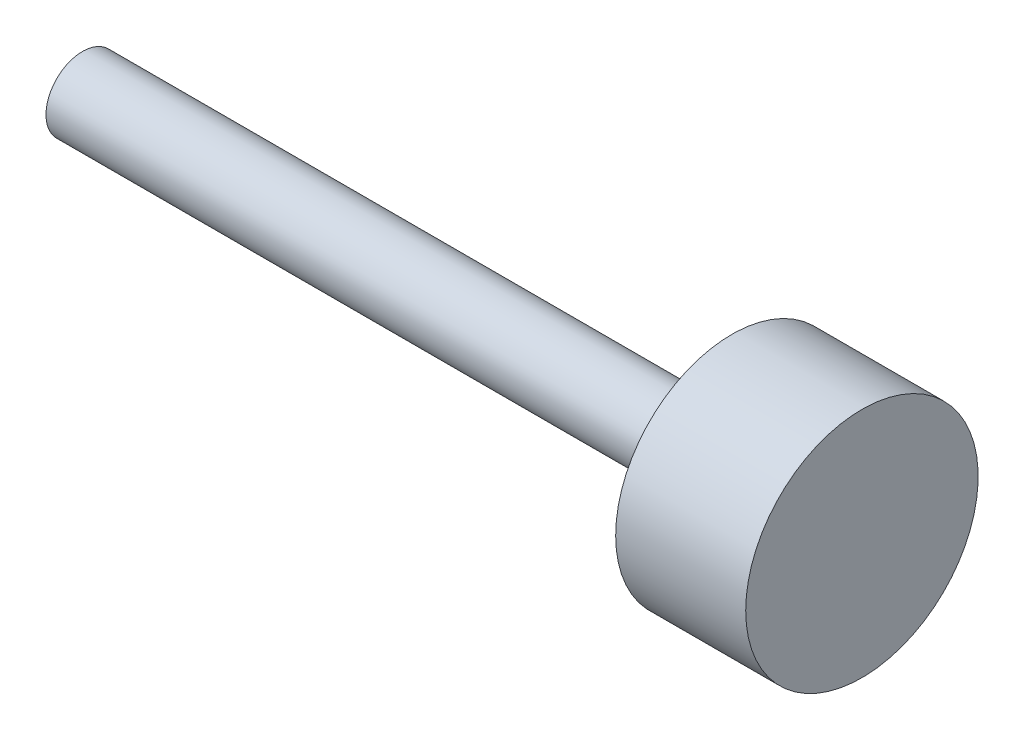
SolidWorks part; units mm, degrees
ref_plane "Front Plane" through (0, 0, 0) normal (0, 0, 1) x (1, 0, 0)
ref_plane "Top Plane" through (0, 0, 0) normal (0, 1, 0) x (1, 0, 0)
ref_plane "Right Plane" through (0, 0, 0) normal (1, 0, 0) x (0, 0, -1)
ref_plane "Plane1" through (-20.5232, 0, 0) normal (1, 0, 0) x (0, 0, -1)
ref_plane "Plane2" through (-20.5232, 0, 0) normal (1, 0, 0) x (0, 0, -1)
sketch "Sketch1" plane through (0, 0, 0) normal (0, 0, 1) x (1, 0, 0)
  line L0 (-22.225, 0) -> (-22.225, 8.001)
  line L1 (-22.225, 8.001) -> (119.9642, 8.001)
  line L2 (119.9642, 8.001) -> (119.9642, 25.4508)
  line L3 (119.9642, 25.4508) -> (148.4376, 25.4508)
  line L4 (148.4376, 25.4508) -> (148.4376, 0)
  line L5 (148.4376, 0) -> (-22.225, 0)
  line L6 (148.4376, 0) -> (-22.225, 0) construction
revolve "Revolve1" add sketch "Sketch1" angle 360 about L6 reverse direction yes
hole_wizard "Hole1" positions "Sketch3" profile "Sketch2" legacy
sketch "Sketch3" plane through (-22.225, 0, 0) normal (-1, 0, 0) x (0, 0, 1)
  point P0 (0, 0)
sketch "Sketch2" plane through (-22.225, 0, 0) normal (0, 1, 0) x (0, 0, 1)
  line L0 (0, 0) -> (0, 30.8737)
  line L1 (0, 30.8737) -> (4.8692, 28.0625)
  line L2 (4.8692, 28.0625) -> (4.8692, 0.6871)
  line L3 (4.8692, 0.6871) -> (5.5562, 0)
  line L4 (5.5562, 0) -> (0, 0)
  line L5 (0, -14.3089) -> (0, 102.4216) construction
  line L6 (0, 30.8737) -> (-4.8692, 28.0625) construction
  line L7 (-4.8692, 0.6871) -> (-5.5562, 0) construction
  dimension "Diameter" = 9.7384
  dimension "Depth" = 28.0625
  dimension "C-Sink Diameter" = 11.1125
  dimension "C-Sink Angle" = 90
  dimension "Drill Angle" = 120
cosmetic thread "Cosmetic Thread1"
ref_plane "Plane3" through (-20.5232, 0, 0) normal (1, 0, 0) x (0, 0, -1)
ref_plane "i1 XY" through (0, 0, 0) normal (0, 0, 1) x (1, 0, 0)
ref_plane "i1 XZ" through (0, 8.001, 0) normal (0, -1, 0) x (-1, 0, 0)
ref_plane "i1 YZ" through (119.9642, 0, 0) normal (1, 0, 0) x (0, 0, -1)
ref_axis "i1 X" through (-80.9, 8.001, 0) along (1, 0, 0)
ref_axis "i1 Y" through (119.9642, -50, 0) along (0, 1, 0)
ref_axis "i1 Z" through (119.9642, 8.001, 80.9) along (0, 0, -1)
sketch3d "i1"
  point P0 (119.9642, 8.001, 0)
ref_plane "i2 XY" through (0, 0, 0) normal (0, 0, 1) x (1, 0, 0)
ref_plane "i2 XZ" through (0, -8.001, 0) normal (0, -1, 0) x (-1, 0, 0)
ref_plane "i2 YZ" through (119.9642, 0, 0) normal (1, 0, 0) x (0, 0, -1)
ref_axis "i2 X" through (-80.9, -8.001, 0) along (1, 0, 0)
ref_axis "i2 Y" through (119.9642, -50, 0) along (0, 1, 0)
ref_axis "i2 Z" through (119.9642, -8.001, 80.9) along (0, 0, -1)
sketch3d "i2"
  point P0 (119.9642, -8.001, 0)
ref_plane "to_rod_guide XY" through (-20.5232, 0, 0) normal (-1, 0, 0) x (0, 0, 1)
ref_plane "to_rod_guide XZ" through (0, 0, 0) normal (0, 1, 0) x (1, 0, 0)
ref_plane "to_rod_guide YZ" through (0, 0, 0) normal (0, 0, -1) x (-1, 0, 0)
ref_axis "to_rod_guide X" through (-20.5232, 0, 80.9) along (0, 0, -1)
ref_axis "to_rod_guide Y" through (-20.5232, 50, 0) along (0, -1, 0)
ref_axis "to_rod_guide Z" through (-80.9, 0, 0) along (1, 0, 0)
sketch3d "to_rod_guide"
  point P0 (-20.5232, 0, 0)
ref_plane "to_stud XY" through (-20.5232, 0, 0) normal (1, 0, 0) x (0, 0, -1)
ref_plane "to_stud XZ" through (0, 0, 0) normal (0, -1, 0) x (-1, 0, 0)
ref_plane "to_stud YZ" through (0, 0, 0) normal (0, 0, -1) x (-1, 0, 0)
ref_axis "to_stud X" through (-20.5232, 0, 80.9) along (0, 0, -1)
ref_axis "to_stud Y" through (-20.5232, -50, 0) along (0, 1, 0)
ref_axis "to_stud Z" through (80.9, 0, 0) along (-1, 0, 0)
sketch3d "to_stud"
  point P0 (-20.5232, 0, 0)
ref_plane "to_stud_old XY" through (-20.5232, 0, 0) normal (1, 0, 0) x (0, 0, -1)
ref_plane "to_stud_old XZ" through (0, 0, 0) normal (0, -1, 0) x (-1, 0, 0)
ref_plane "to_stud_old YZ" through (0, 0, 0) normal (0, 0, -1) x (-1, 0, 0)
ref_axis "to_stud_old X" through (-20.5232, 0, 80.9) along (0, 0, -1)
ref_axis "to_stud_old Y" through (-20.5232, -50, 0) along (0, 1, 0)
ref_axis "to_stud_old Z" through (80.9, 0, 0) along (-1, 0, 0)
sketch3d "to_stud_old"
  point P0 (-20.5232, 0, 0)
